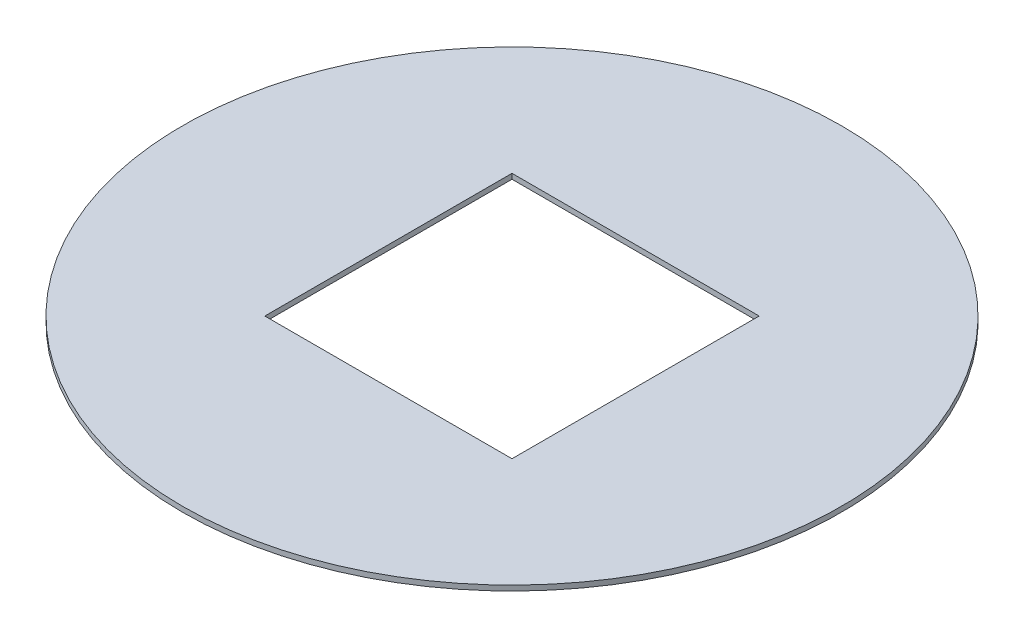
SolidWorks part; units mm, degrees
material "Thornel VCB-20 Carbon Cloth"
ref_plane "Front Plane" through (0, 0, 0) normal (0, 0, 1) x (1, 0, 0)
ref_plane "Top Plane" through (0, 0, 0) normal (0, 1, 0) x (1, 0, 0)
ref_plane "Right Plane" through (0, 0, 0) normal (1, 0, 0) x (0, 0, -1)
sketch "Sketch1" plane through (0, 0, 0) normal (0, 0, 1) x (1, 0, 0)
  line L0 (-60, -0.785) -> (-100, -0.785) construction
  line L1 (-60, 0.785) -> (-60, -0.785) construction
  line L2 (-60, 0.785) -> (-100, 0.785) construction
  line L3 (-100, 0.785) -> (-100, -0.785) construction
  line L4 (-60, -0.785) -> (-100, -0.785)
  line L5 (-60, 0.785) -> (-60, -0.785)
  line L6 (-60, 0.785) -> (-100, 0.785)
  line L7 (-100, 0.785) -> (-100, -0.785)
  line L8 (0, -200069.0475) -> (0, 200086.9028) construction
  line L9 (0, -200069.0475) -> (0, 200086.9028) construction
revolve "Revolve1" add sketch "Sketch1" angle 360 about L9
sketch "Sketch2" plane through (0, 0.785, 0) normal (0, 1, 0) x (1, 0, 0)
  line L1 (-37.5, -37.5) -> (37.5, -37.5)
  line L2 (-37.5, -37.5) -> (-37.5, 37.5)
  line L3 (-37.5, 37.5) -> (37.5, 37.5)
  line L4 (37.5, -37.5) -> (37.5, 37.5)
  line L5 (-37.5, -37.5) -> (37.5, 37.5) construction
  line L6 (-37.5, 37.5) -> (37.5, -37.5) construction
  circle A0 centre (0, 0) radius 60 construction
  circle A1 centre (0, 0) radius 60
  dimension "D1" = 75
  dimension "D2" = 75
extrude "Boss-Extrude1" add sketch "Sketch2" against normal up to surface (1.57 mm away) up to face at (0, -0.785, -60)
